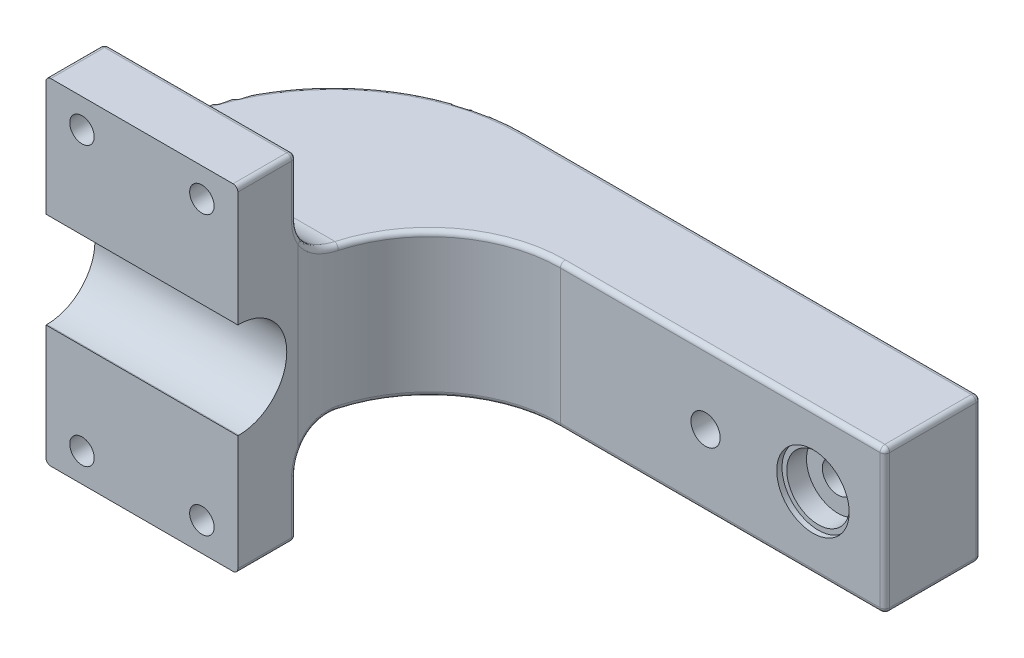
SolidWorks part; units mm, degrees
material "PLA"
ref_plane "Plan de face" through (0, 0, 0) normal (0, 0, 1) x (1, 0, 0)
ref_plane "Plan de dessus" through (0, 0, 0) normal (0, 1, 0) x (1, 0, 0)
ref_plane "Plan de droite" through (0, 0, 0) normal (1, 0, 0) x (0, 0, -1)
sketch "Esquisse1" plane through (0, 0, 0) normal (0, 0, 1) x (1, 0, 0)
  line L1 (-15, 15) -> (15, 15)
  line L2 (-15, 15) -> (-15, -15)
  line L3 (-15, -15) -> (15, -15)
  line L4 (15, 15) -> (15, -15)
  line L5 (-15, 15) -> (15, -15) construction
  line L6 (-15, -15) -> (15, 15) construction
  point P0 (0, 0)
  dimension "D1" = 30
  dimension "D2" = 30
extrude "Boss.-Extru.1" add sketch "Esquisse1" along normal blind 20
sketch "Esquisse2" plane through (0, 0, 20) normal (0, 0, 1) x (1, 0, 0)
  circle A0 centre (0, 0) radius 7.55
  dimension "D1" = 15.1
extrude "Enlèv. mat.-Extru.1" cut sketch "Esquisse2" against normal blind 1.1
sketch "Esquisse3" plane through (0, 0, 18.9) normal (0, 0, 1) x (1, 0, 0)
  circle A0 centre (0, 0) radius 6.55
  dimension "D1" = 13.1
extrude "Enlèv. mat.-Extru.2" cut sketch "Esquisse3" against normal blind 4.1
sketch "Esquisse4" plane through (0, 0, 14.8) normal (0, 0, 1) x (1, 0, 0)
  circle A0 centre (0, 0) radius 3.25
  dimension "D1" = 6.5
extrude "Enlèv. mat.-Extru.3" cut sketch "Esquisse4" against normal through all
ref_plane "Plan2" through (0, 0, 59.7) normal (0, 0, 1) x (1, 0, 0)
sketch "Esquisse5" plane through (0, 0, 59.7) normal (0, 0, 1) x (1, 0, 0)
  line L0 (0, 0) -> (-90, 0) construction
  line L2 (-100, 15) -> (-80, 15)
  line L3 (-100, 15) -> (-100, -15)
  line L4 (-100, -15) -> (-80, -15)
  line L5 (-80, 15) -> (-80, -15)
  line L6 (-100, 15) -> (-80, -15) construction
  line L7 (-100, -15) -> (-80, 15) construction
  line L8 (-100, 15) -> (-120, 15)
  line L9 (-100, 15) -> (-100, -15)
  line L10 (-100, -15) -> (-120, -15)
  line L11 (-120, 15) -> (-120, -15)
  dimension "D1" = 90
  dimension "D2" = 30
  dimension "D3" = 20
  dimension "D4" = 20
extrude "Boss.-Extru.2" add sketch "Esquisse5" against normal blind 12.35 contours L8 L11 L10 L3 | L5 L2 L3 L4 region at (-90, 0, 59.7) region at (-110, 0, 59.7)
sketch "Esquisse6" plane through (0, 15, 0) normal (0, 1, 0) x (1, 0, 0)
  line L0 (-80, -59.7) -> (-27.65, -59.7) construction
  line L1 (-15, -20) -> (-52.65, -20)
  line L6 (-15, -20) -> (-15, 0)
  line L10 (-27.65, -59.7) -> (7.0557, -94.4057) construction
  line L12 (-80, -59.7) -> (-80, -47.35)
  line L15 (-120, -59.7) -> (-120, -40)
  line L16 (-15, 0) -> (-80, 0)
  line L17 (-80, -59.7) -> (-120, -59.7) construction
  line L18 (-80, -59.7) -> (-120, -59.7)
  line L19 (-80, -47.35) -> (-120, -47.35) construction
  arc A6 (-52.65, -20) -> (-80, -47.35) centre (-52.65, -47.35) ccw
  arc A7 (-120, -40) -> (-80, 0) centre (-80, -40) cw
  dimension "D2" = 40
  dimension "D3" = 27.35
  dimension "D1" = 45
extrude "Boss.-Extru.3" add sketch "Esquisse6" against normal up to surface (30 mm away) up to face at (0, -15, 10)
sketch "Esquisse12" plane through (0, 0, 0) normal (0, 0, -1) x (-1, 0, 0)
  line L0 (-15, -15) -> (-15, 15) construction
  line L1 (80, -15) -> (-15, -15) construction
  circle A0 centre (22.3901, 0) radius 3.05
  dimension "D1" = 6.1
  dimension "D2" = 37.3901
  dimension "D3" = 15
extrude "Enlèv. mat.-Extru.7" cut sketch "Esquisse12" against normal through all contours A0
sketch "Esquisse13" plane through (-120, 0, 0) normal (-1, 0, 0) x (0, 0, 1)
  line L0 (59.7, -15) -> (59.7, 15) construction
  arc A0 (59.7, 10) -> (59.7, -10) centre (59.7, 0) ccw
  dimension "D1" = 10
extrude "Enlèv. mat.-Extru.8" cut sketch "Esquisse13" against normal through all and the other way through all
sketch "Esquisse14" plane through (0, 0, 59.7) normal (0, 0, 1) x (1, 0, 0)
  line L0 (-120, 15) -> (-120, 35)
  line L1 (-120, 35) -> (-80, 35)
  line L2 (-80, 15) -> (-80, 35)
  line L3 (-120, 15) -> (-80, 15) construction
  line L4 (-120, 15) -> (-80, 15)
  line L5 (-100, 15) -> (-100, 20.6695) construction
  line L6 (-120, 0) -> (-95.0921, 0) construction
  line L7 (-120, 10) -> (-120, -10) construction
  line L8 (-120, -15) -> (-120, -35)
  line L9 (-120, -35) -> (-80, -35)
  line L10 (-80, -15) -> (-80, -35)
  line L11 (-120, -15) -> (-80, -15)
  circle A0 centre (-112.5, 29) radius 2.55
  circle A1 centre (-87.5, 29) radius 2.55
  circle A2 centre (-87.5, -29) radius 2.55
  circle A3 centre (-112.5, -29) radius 2.55
  dimension "D2" = 5.1
  dimension "D1" = 20
  dimension "D3" = 6
  dimension "D4" = 7.5
extrude "Boss.-Extru.4" add sketch "Esquisse14" against normal blind 12 contours L4 L2 L1 L0 | L8 L9 L10 L11 | A1 | A0 | A3 | A2
fillet "Congé1" radius 8 2 edges at (-100, -15, 47.7) (-100, 15, 47.7)
fillet "Congé2" radius 1 30 edges at (-18.825, -15, 20) (-80, -29, 47.7) (-80, -21.8168, 47.612) (-79.8227, -16.4134, 44.2405) (-120, -29, 47.7) (-120, -17.4502, 45.4619) (-108.178, -15, 11.6099) (-18.825, 15, 20) (-69.0633, 15, 25.4725) (-79.8608, 16.6717, 44.5942) (-80, 21.8168, 47.612) (-32.5, 15, 0) (-108.178, 15, 11.6099) (-120, 17.4502, 45.4619) (15, -15, 10) (15, 15, 10) (15, 0, 20) (15, 0, 0) (-80, 35, 53.7) (-120, 35, 53.7) (-80, -35, 53.7) (-120, -35, 53.7) (-100, -35, 47.7) (-69.0633, -15, 25.4725) (-32.5, -15, 0) (-80, 29, 47.7) (-100, 35, 47.7) (-120, 29, 47.7)
sketch "Esquisse16" plane through (0, 0, 59.7) normal (0, 0, 1) x (1, 0, 0)
  line L4 (-80, 10) -> (-80, 34)
  line L5 (-81, 35) -> (-119, 35)
  line L6 (-120, 34) -> (-120, 10)
  line L7 (-120, 10) -> (-80, 10)
  line L8 (-80, 10) -> (-80, 34)
  line L9 (-81, 35) -> (-119, 35)
  line L10 (-120, 34) -> (-120, 10)
  line L11 (-120, 10) -> (-80, 10)
  line L12 (-119, -35) -> (-81, -35)
  line L13 (-80, -34) -> (-80, -10)
  line L14 (-80, -10) -> (-120, -10)
  line L15 (-120, -10) -> (-120, -34)
  line L16 (-119, -35) -> (-81, -35)
  line L17 (-80, -34) -> (-80, -10)
  line L18 (-80, -10) -> (-120, -10)
  line L19 (-120, -10) -> (-120, -34)
  circle A0 centre (-87.5, 29) radius 2.55 construction
  circle A1 centre (-112.5, 29) radius 2.55 construction
  arc A2 (-80, 34) -> (-81, 35) centre (-81, 34) ccw
  arc A3 (-119, 35) -> (-120, 34) centre (-119, 34) ccw
  arc A4 (-80, 34) -> (-81, 35) centre (-81, 34) ccw
  arc A5 (-119, 35) -> (-120, 34) centre (-119, 34) ccw
  arc A6 (-81, -35) -> (-80, -34) centre (-81, -34) ccw
  arc A7 (-120, -34) -> (-119, -35) centre (-119, -34) ccw
  arc A8 (-81, -35) -> (-80, -34) centre (-81, -34) ccw
  arc A9 (-120, -34) -> (-119, -35) centre (-119, -34) ccw
  circle A10 centre (-87.5, 29) radius 2.55
  circle A11 centre (-112.5, 29) radius 2.55
  circle A12 centre (-87.5, -29) radius 2.55 construction
  circle A13 centre (-112.5, -29) radius 2.55 construction
  circle A14 centre (-87.5, -29) radius 2.55
  circle A15 centre (-112.5, -29) radius 2.55
  dimension "D1" = 0
  dimension "D2" = 0
extrude "Boss.-Extru.5" add sketch "Esquisse16" along normal blind 0.2
sketch "Esquisse17" [suppressed] plane through (0, 0, 20) normal (0, 0, 1) x (1, 0, 0)
  circle A3 centre (0, 0) radius 3.25
  circle A4 centre (0, 0) radius 7.5
  circle M8 centre (0, 0) radius 7.5
  dimension "D1" = 15
  dimension "D2" = 6.5
extrude "Boss.-Extru.6" [suppressed] add sketch "Esquisse17" against normal up to next contours A3 M8 | A4
sketch "Esquisse18" [suppressed] plane through (0, 0, 20) normal (0, 0, 1) x (1, 0, 0)
  circle A0 centre (-22.3901, 0) radius 7.5
  dimension "D1" = 15
extrude "Enlèv. mat.-Extru.9" [suppressed] cut sketch "Esquisse18" against normal blind 1
sketch "Esquisse20" [suppressed] plane through (0, 0, 19) normal (0, 0, 1) x (1, 0, 0)
  circle A0 centre (-22.3901, 0) radius 6.5
  dimension "D1" = 13
extrude "Enlèv. mat.-Extru.10" [suppressed] cut sketch "Esquisse20" against normal blind 4
